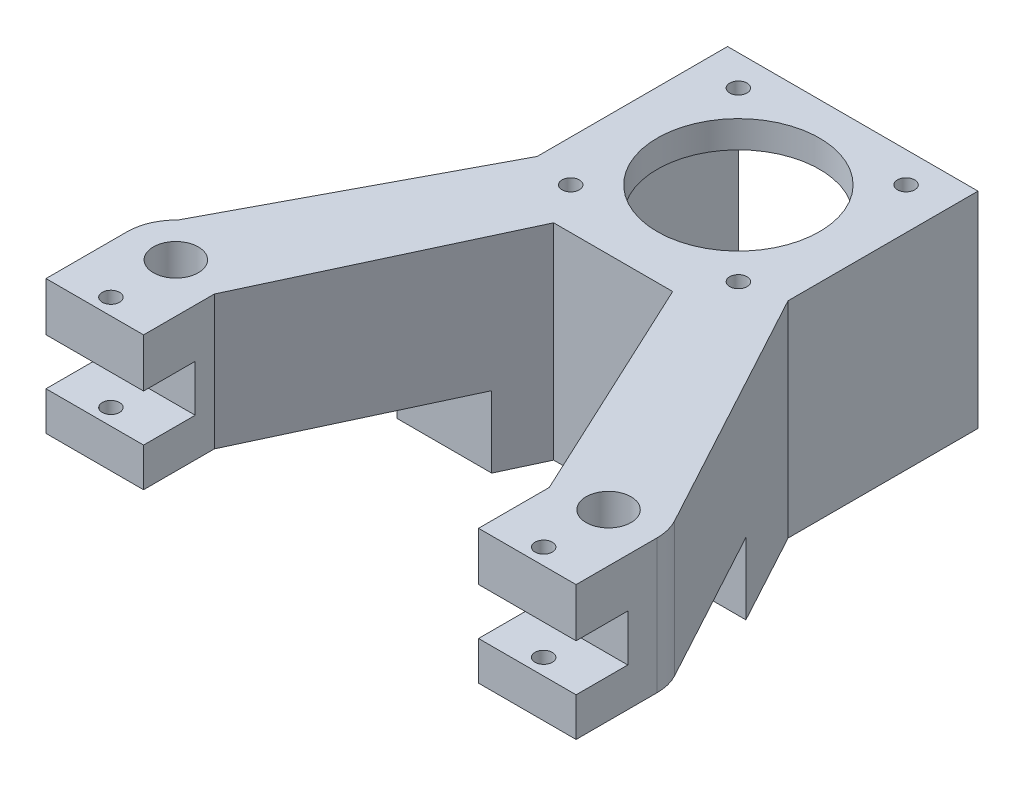
SolidWorks part; units mm, degrees
note: The reader was unsure of these and kept them because the rebuilt part matched: shared geometry of "草图7<7>", "草图7<8>".
ref_plane "前视基准面" through (0, 0, 0) normal (0, 0, 1) x (1, 0, 0)
ref_plane "上视基准面" through (0, 0, 0) normal (0, 1, 0) x (1, 0, 0)
ref_plane "右视基准面" through (0, 0, 0) normal (1, 0, 0) x (0, 0, -1)
sketch "草图6" plane through (0, 0, 0) normal (0, 1, 0) x (1, 0, 0)
  line L1 (-21.15, -21.15) -> (21.15, -21.15)
  line L2 (-21.15, -21.15) -> (-21.15, 21.15)
  line L3 (-21.15, 21.15) -> (21.15, 21.15)
  line L5 (0, 21.15) -> (0, -21.15) construction
  line L6 (-21.15, 0) -> (21.15, 0) construction
  line L8 (21.15, 21.15) -> (21.15, -21.15)
  circle A0 centre (15.5, 15.5) radius 1.6
  circle A1 centre (-15.5, 15.5) radius 1.6
  circle A2 centre (-15.5, -15.5) radius 1.6
  circle A3 centre (15.5, -15.5) radius 1.6
  circle A4 centre (0, 0) radius 15
  point P0 (0, 0)
extrude "凸台-拉伸1" add sketch "草图6" along normal blind 5
sketch "草图7" plane through (0, 5, 0) normal (0, 1, 0) x (1, 0, 0)
  line L0 (49, -65) -> (49, -79)
  line L1 (49, -79) -> (30.9639, -79)
  line L2 (21, -10) -> (47.9146, -59.7152)
  line L3 (49, -64) -> (49, -65)
  line L4 (-10, -21) -> (-30.9639, -65.9194)
  line L5 (-21, -10) -> (-46.2023, -57.4784)
  line L6 (10, -21) -> (30.9639, -65.9194)
  line L7 (30.9639, -79) -> (30.9639, -65.9194)
  line L8 (-49, -64) -> (-49, -79)
  line L9 (-30.9639, -65.9194) -> (-30.9639, -79)
  line L13 (-30.9639, -79) -> (-49, -79)
  arc A0 (-46.2023, -57.4784) -> (-49, -64) centre (-40, -64) ccw
  arc A1 (49, -64) -> (47.9146, -59.7152) centre (40, -64) ccw
  circle A2 centre (-40, -64) radius 4.15
  circle A3 centre (40, -64) radius 4.15
  circle A4 centre (40, -76) radius 1.6
  circle A5 centre (-40, -76) radius 1.6
  dimension "D1" = 18
  dimension "D2" = 18
extrude "凸台-拉伸5" add sketch "草图7" against normal blind 38
extrude "凸台-拉伸7" add sketch "草图7<7>" against normal blind 38 contours A1 A3
sketch "草图7<7>" plane through (0, 5, 0) normal (0, 1, 0) x (1, 0, 0) same geometry as "草图7"
extrude "凸台-拉伸8" add sketch "草图7<8>" against normal blind 38 contours A0 A2
sketch "草图7<8>" plane through (0, 5, 0) normal (0, 1, 0) x (1, 0, 0) same geometry as "草图7"
sketch "草图12" plane through (0, 5, 0) normal (0, 1, 0) x (1, 0, 0)
  line L0 (21.15, 21.15) -> (23.15, 21.15)
  line L1 (21.15, 21.15) -> (21.15, -23.15)
  line L2 (23.15, 21.15) -> (23.15, -23.15)
  line L3 (21.15, -23.15) -> (23.15, -23.15)
extrude "凸台-拉伸11" add sketch "草图12" against normal blind 38
sketch "草图14" plane through (0, 5, 0) normal (0, 1, 0) x (1, 0, 0)
  line L0 (21.15, -23.15) -> (-23.15, -23.15)
  line L1 (21.15, -23.15) -> (21.15, -21.15)
  line L2 (-23.15, -23.15) -> (-23.15, -21.15)
  line L3 (21.15, -21.15) -> (-23.15, -21.15)
extrude "凸台-拉伸12" add sketch "草图14" against normal blind 38
sketch "草图15" plane through (0, 5, 0) normal (0, 1, 0) x (1, 0, 0)
  line L0 (-23.15, -21.15) -> (-23.15, 21.15)
  line L1 (-23.15, -21.15) -> (-21.15, -21.15)
  line L2 (-23.15, 21.15) -> (-21.15, 21.15)
  line L3 (-21.15, -21.15) -> (-21.15, 21.15)
extrude "凸台-拉伸13" add sketch "草图15" against normal blind 38
sketch "草图17" plane through (0, -33, 0) normal (0, -1, 0) x (1, 0, 0)
  line L1 (62.0405, 30.9533) -> (-8.6048, 30.9533)
  line L2 (62.0405, 30.9533) -> (62.0405, 85.063)
  line L3 (62.0405, 85.063) -> (-8.6048, 85.063)
  line L5 (-8.6048, 30.9533) -> (-61.8372, 30.9533)
  line L7 (-8.6048, 85.063) -> (-61.8372, 85.063)
  line L8 (-61.8372, 30.9533) -> (-61.8372, 85.063)
extrude "切除-拉伸1" cut sketch "草图17" against normal blind 13.2
sketch "草图18" plane through (49, 0, 0) normal (1, 0, 0) x (0, 0, -1)
  line L0 (-79, -19.8) -> (-79, 5) construction
  line L1 (-79, -4) -> (-69.4505, -4)
  line L2 (-79, -4) -> (-79, -12.6432)
  line L3 (-79, -12.6432) -> (-69.4505, -12.6432)
  line L4 (-69.4505, -4) -> (-69.4505, -12.6432)
extrude "切除-拉伸2" cut sketch "草图18" against normal blind 123
